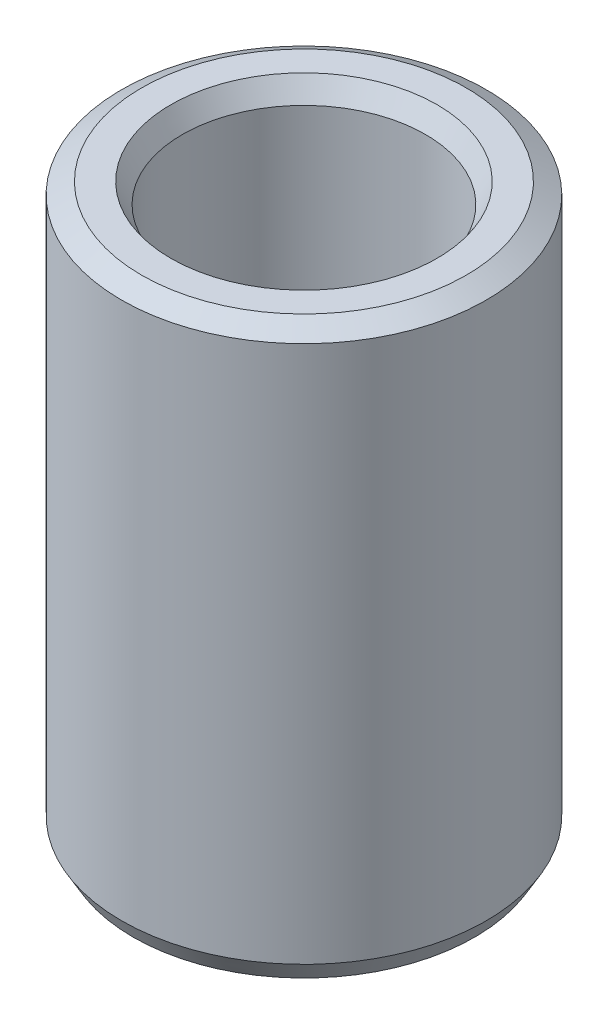
SolidWorks part; units mm, degrees
ref_plane "Front Plane" through (0, 0, 0) normal (0, 0, 1) x (1, 0, 0)
ref_plane "Top Plane" through (0, 0, 0) normal (0, 1, 0) x (1, 0, 0)
ref_plane "Right Plane" through (0, 0, 0) normal (1, 0, 0) x (0, 0, -1)
sketch "Sketch1" plane through (0, 0, 0) normal (0, 1, 0) x (1, 0, 0)
  circle A0 centre (0, 0) radius 17.5
  dimension "SLEEVE_OD" = 35
extrude "Boss-Extrude1" add sketch "Sketch1" along normal blind 54.6246
sketch "Sketch2" plane through (0, 0, 0) normal (0, 1, 0) x (1, 0, 0)
  circle A0 centre (0, 0) radius 11.6695
  dimension "BORE_D" = 23.339
extrude "Cut-Extrude1" cut sketch "Sketch2" along normal through all
chamfer "Chamfer1" distance 1.1095 angle 60 4 edges at (0, 54.6246, 11.6695) (0, 0, 11.6695) (0, 0, 17.5) (0, 54.6246, 17.5) first distance on face at (0, 54.6246, 11.6695) first distance on face at (0, 0, 11.6695) first distance on face at (0, 54.6246, 17.5)
